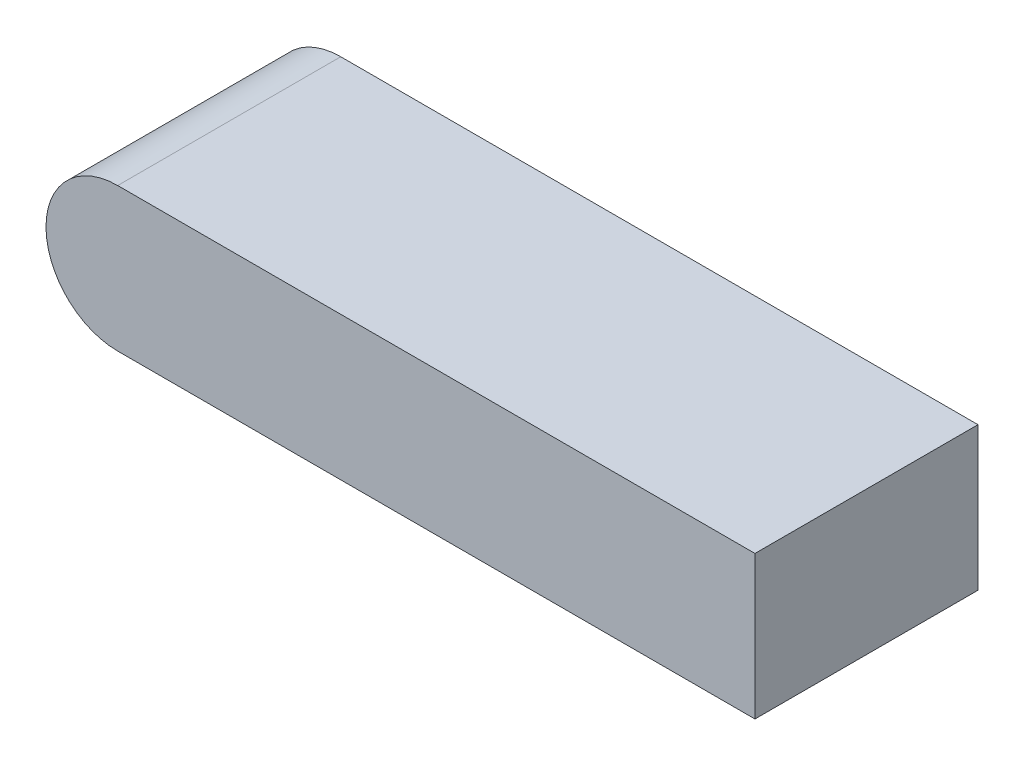
SolidWorks part; units mm, degrees
ref_plane "Front Plane" through (0, 0, 0) normal (0, 0, 1) x (1, 0, 0)
ref_plane "Top Plane" through (0, 0, 0) normal (0, 1, 0) x (1, 0, 0)
ref_plane "Right Plane" through (0, 0, 0) normal (1, 0, 0) x (0, 0, -1)
sketch "Sketch1" plane through (0, 0, 0) normal (0, 1, 0) x (1, 0, 0)
  line L1 (-63.5, -22.225) -> (63.5, -22.225)
  line L2 (-63.5, -22.225) -> (-63.5, 22.225)
  line L3 (-63.5, 22.225) -> (63.5, 22.225)
  line L4 (63.5, -22.225) -> (63.5, 22.225)
  line L5 (-63.5, -22.225) -> (63.5, 22.225) construction
  line L6 (-63.5, 22.225) -> (63.5, -22.225) construction
  point P0 (0, 0)
  dimension "D1" = 44.45
  dimension "D2" = 127
extrude "Boss-Extrude1" add sketch "Sketch1" along normal mid plane 28.575
sketch "Sketch2" plane through (0, 0, -22.225) normal (0, 0, -1) x (-1, 0, 0)
  line L0 (63.5, 14.2875) -> (63.5, -14.2875) construction
  line L1 (63.5, -14.2875) -> (63.5, 14.2875)
  arc A0 (63.5, 14.2875) -> (63.5, -14.2875) centre (63.5, 0) cw
extrude "Boss-Extrude2" add sketch "Sketch2" against normal up to surface (44.45 mm away) up to face at (0, 0, 22.225)
